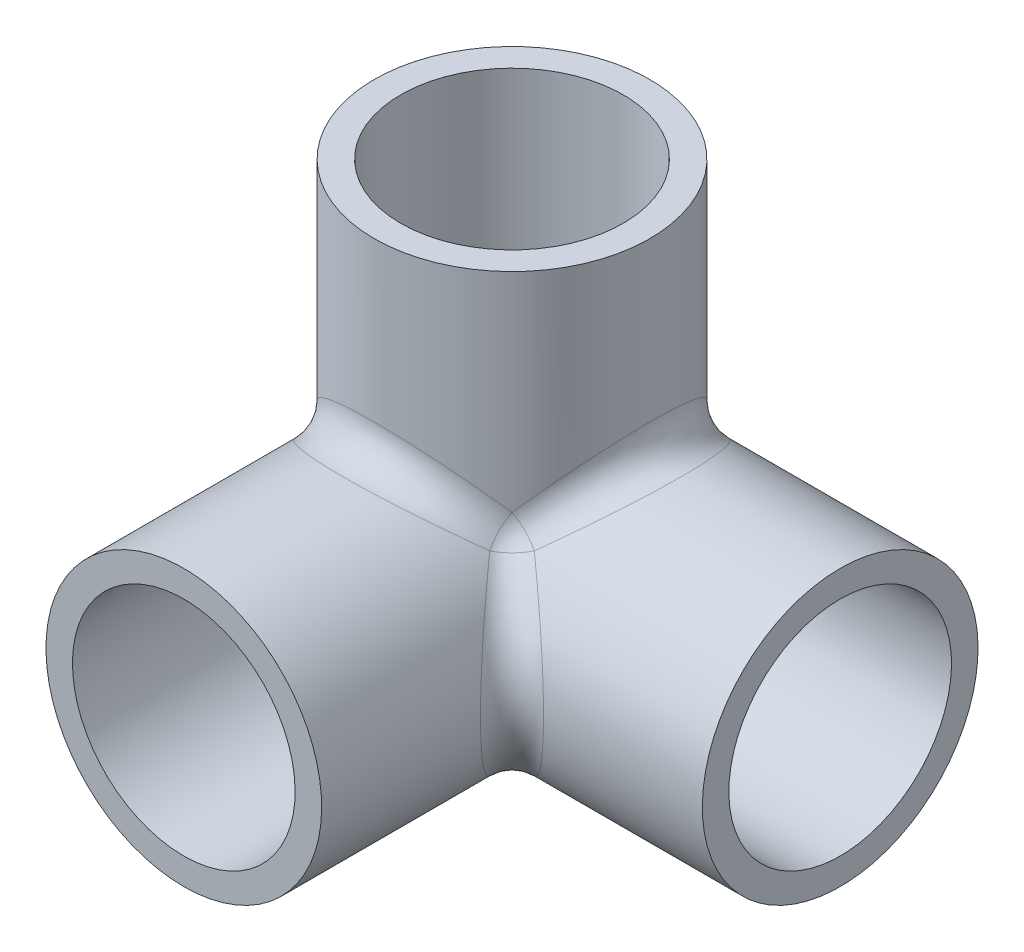
SolidWorks part; units mm, degrees
ref_plane "Front Plane" through (0, 0, 0) normal (0, 0, 1) x (1, 0, 0)
ref_plane "Top Plane" through (0, 0, 0) normal (0, 1, 0) x (1, 0, 0)
ref_plane "Right Plane" through (0, 0, 0) normal (1, 0, 0) x (0, 0, -1)
sketch "Sketch1" plane through (0, 0, 0) normal (1, 0, 0) x (0, 0, -1)
  line L0 (0, 0) -> (-39.6875, 0) construction
  line L1 (0, 0) -> (0, 39.6875) construction
  line L2 (-39.6875, 16.6687) -> (-39.6875, -16.6688) construction
  line L3 (-16.6687, 39.6875) -> (16.6687, 39.6875) construction
  line L4 (-14.2875, -10.4648) -> (-14.2875, 10.4648) construction
  line L5 (-10.4648, 14.2875) -> (10.4648, 14.2875) construction
  line L6 (-14.2875, -10.4648) -> (-39.6875, -10.4648) construction
  line L7 (-26.9875, 13.462) -> (-26.9875, -13.462) construction
  line L8 (10.4648, 14.2875) -> (10.4648, 39.6875) construction
  line L9 (-13.462, 26.9875) -> (13.462, 26.9875) construction
  point P3 (-26.9875, -10.4648)
  point P7 (-39.6875, 0)
  point P10 (0, 39.6875)
  point P13 (-14.2875, 0)
  point P16 (0, 14.2875)
  point P20 (-26.9875, 0)
  point P21 (10.4648, 26.9875)
  point P25 (0, 26.9875)
  dimension "Leg Length" = 39.6875
  dimension "Elbow OD" = 33.3375
  dimension "Center to Socket" = 14.2875
  dimension "Pipe ID" = 20.9296
  dimension "For Pipe OD" = 26.924
  dimension "D1" = 14.2875
sketch "Sketch2" plane through (0, 0, 0) normal (0, 0, 1) x (1, 0, 0)
  line L0 (0, 0) -> (39.6875, 0) construction
  line L1 (0, 13.462) -> (0, -13.462) construction
  line L2 (39.6875, -16.6687) -> (39.6875, 16.6687) construction
  line L3 (14.2875, -10.4648) -> (14.2875, 10.4648) construction
  line L4 (26.9875, -13.462) -> (26.9875, 13.462) construction
  line L5 (0, 0) -> (0, 39.6875) construction
  line L6 (14.2875, 10.4648) -> (39.6875, 10.4648) construction
  point P7 (39.6875, 0)
  point P10 (14.2875, 0)
  point P13 (26.9875, 0)
  point P15 (26.9875, 10.4648)
  dimension "D1" = 14.2875
  dimension "D2" = 20.9296
  dimension "D3" = 33.3375
  dimension "D4" = 39.6875
  dimension "D5" = 26.924
sketch "Sketch3" plane through (0, 0, 0) normal (1, 0, 0) x (0, 0, -1)
  line L0 (-39.6875, 0) -> (-39.6875, -16.6688)
  line L1 (-39.6875, -16.6688) -> (0, -16.6688)
  line L2 (0, -16.6687) -> (0, 16.6687) construction
  line L3 (-39.6875, 0) -> (16.6687, 0)
  arc A0 (0, -16.6688) -> (16.6687, 0) centre (0, 0) ccw
revolve "Revolve1" add sketch "Sketch3" angle 360 about L3
sketch "Sketch4" plane through (0, 0, 0) normal (1, 0, 0) x (0, 0, -1)
  line L0 (16.6687, 39.6875) -> (0, 39.6875)
  line L1 (0, 39.6875) -> (0, -16.6687)
  line L2 (0, -16.6687) -> (0, 16.6687) construction
  line L3 (16.6687, 39.6875) -> (16.6687, 0)
  arc A0 (0, -16.6688) -> (0, 16.6688) centre (0, 0) ccw construction
  arc A1 (0, -16.6687) -> (16.6687, 0) centre (0, 0) ccw
revolve "Revolve2" add sketch "Sketch4" angle 360 about L1
sketch "Sketch5" plane through (0, 0, 0) normal (0, 0, 1) x (1, 0, 0)
  line L0 (39.6875, -16.6687) -> (0, -16.6688)
  line L1 (0, 16.6687) -> (0, -16.6688) construction
  line L2 (39.6875, -16.6687) -> (39.6875, 0)
  line L3 (39.6875, 0) -> (-16.6687, 0)
  circle A0 centre (0, 0) radius 16.6688 construction
  arc A1 (-16.6687, 0) -> (0, -16.6688) centre (0, 0) ccw
revolve "Revolve3" add sketch "Sketch5" angle 360 about L3
sketch "Sketch6" plane through (0, 0, 0) normal (1, 0, 0) x (0, 0, -1)
  line L0 (-39.6875, 0) -> (10.4648, 0)
  line L1 (-39.6875, -13.462) -> (-14.2875, -13.462)
  line L2 (-39.6875, 16.6687) -> (-39.6875, -16.6688) construction
  line L3 (-14.2875, -13.462) -> (-14.2875, -10.4648)
  line L4 (-14.2875, -10.4648) -> (0, -10.4648)
  line L5 (0, -13.462) -> (0, 13.462) construction
  line L6 (-39.6875, 0) -> (-39.6875, -13.462)
  arc A0 (10.4648, 0) -> (0, -10.4648) centre (0, 0) cw
revolve "Cut-Revolve1" cut sketch "Sketch6" angle 360 about L0
sketch "Sketch7" plane through (0, 0, 0) normal (1, 0, 0) x (0, 0, -1)
  line L0 (0, 39.6875) -> (13.462, 39.6875)
  line L1 (0, 39.6875) -> (0, -10.4648)
  line L2 (0, -13.462) -> (0, 13.462) construction
  line L3 (-16.6687, 39.6875) -> (16.6687, 39.6875) construction
  line L4 (13.462, 39.6875) -> (13.462, 14.2875)
  line L5 (13.462, 14.2875) -> (10.4648, 14.2875)
  line L6 (10.4648, 14.2875) -> (10.4648, 0)
  line L7 (0, 0) -> (-39.6875, 0) construction
  arc A0 (0, -10.4648) -> (10.4648, 0) centre (0, 0) ccw
revolve "Cut-Revolve2" cut sketch "Sketch7" angle 360 about L1
sketch "Sketch8" plane through (0, 0, 0) normal (0, 0, 1) x (1, 0, 0)
  line L0 (39.6875, -13.462) -> (14.2875, -13.462)
  line L1 (39.6875, -16.6687) -> (39.6875, 16.6687) construction
  line L2 (14.2875, -13.462) -> (14.2875, -10.4648)
  line L3 (14.2875, -10.4648) -> (0, -10.4648)
  line L4 (39.6875, -13.462) -> (39.6875, 0)
  line L5 (39.6875, 0) -> (-10.4648, 0)
  arc A0 (-10.4648, 0) -> (10.4648, 0) centre (0, 0) ccw construction
  arc A1 (-10.4648, 0) -> (0, -10.4648) centre (0, 0) ccw
revolve "Cut-Revolve3" cut sketch "Sketch8" angle 360 about L5
fillet "Fillet1" radius 3.81 3 edges at (15.3999, 15.3999, -6.3789) (15.3999, -6.3789, 15.3999) (-6.3789, 15.3999, 15.3999)
sketch "Sketch9" plane through (0, 0, 0) normal (1, 0, 0) x (0, 0, -1)
  line L0 (-39.6875, 13.462) -> (-14.2875, 13.462)
  line L1 (-39.6875, 16.6687) -> (-39.6875, -16.6688) construction
  line L2 (-14.2875, 13.462) -> (-14.2875, 10.4648)
  line L3 (-14.2875, 10.4648) -> (-10.4648, 10.4648)
  line L4 (-10.4648, 10.4648) -> (-10.4648, 14.2875)
  line L5 (-10.4648, 14.2875) -> (-13.462, 14.2875)
  line L6 (-13.462, 14.2875) -> (-13.462, 39.6875)
  line L7 (-16.6687, 39.6875) -> (16.6687, 39.6875) construction
  line L8 (-39.6875, -13.462) -> (-14.2875, -13.462)
  line L9 (-14.2875, -13.462) -> (-14.2875, -10.4648)
  line L10 (-14.2875, -10.4648) -> (0, -10.4648)
  line L11 (10.4648, 0) -> (10.4648, 14.2875)
  line L12 (10.4648, 14.2875) -> (13.462, 14.2875)
  line L13 (13.462, 14.2875) -> (13.462, 39.6875)
  circle A0 centre (0, 0) radius 10.4648 construction
  arc A1 (10.4648, 0) -> (-7.3997, 7.3997) centre (0, 0) ccw construction
  arc A2 (0, -10.4648) -> (10.4648, 0) centre (0, 0) ccw
sketch "Sketch10" plane through (0, 0, 39.6875) normal (0, 0, 1) x (1, 0, 0)
  circle A0 centre (0, 0) radius 13.462 construction
  circle A1 centre (0, 0) radius 13.462
  point P3 (0, -13.462)
  point P4 (13.462, 0)
  point P5 (-13.462, 0)
  point P6 (0, 13.462)
equation "\"D1@Sketch1\"=\"Center to Socket@Sketch1\""
equation "\"D1@Sketch2\"=\"Center to Socket@Sketch1\""
equation "\"D2@Sketch2\"=\"Pipe ID@Sketch1\""
equation "\"D3@Sketch2\"=\"Elbow OD@Sketch1\""
equation "\"D4@Sketch2\"=\"Leg Length@Sketch1\""
equation "\"D5@Sketch2\"=\"For Pipe OD@Sketch1\""
equation "\"D1@Fillet1\"=\"Elbow OD@Sketch1\"*0.1142857143"
